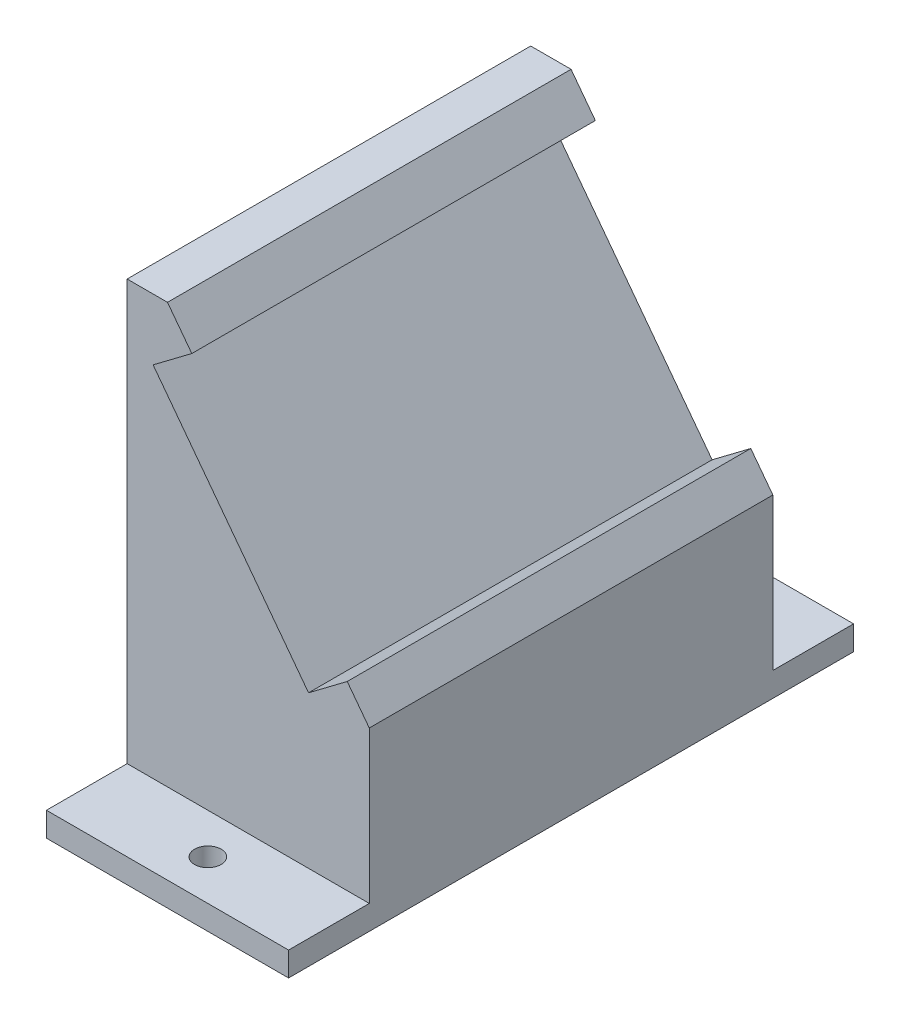
SolidWorks part; units mm, degrees
ref_plane "前视基准面" through (0, 0, 0) normal (0, 0, 1) x (1, 0, 0)
ref_plane "上视基准面" through (0, 0, 0) normal (0, 1, 0) x (1, 0, 0)
ref_plane "右视基准面" through (0, 0, 0) normal (1, 0, 0) x (0, 0, -1)
sketch "草图1" plane through (0, 0, 0) normal (0, 0, 1) x (1, 0, 0)
  line L3 (-10, 55) -> (-15, 55)
  line L4 (-15, 0) -> (-15, 55)
  line L8 (15, 0) -> (15, 21.8239)
  line L9 (-11.7827, 47.3959) -> (7.4753, 21.8396)
  line L10 (-6.9909, 51.0068) -> (-11.7827, 47.3959)
  line L11 (7.4753, 21.8396) -> (12.2672, 25.4505)
  line L12 (-10, 55) -> (-6.9909, 51.0068)
  line L13 (12.2672, 25.4505) -> (15, 21.8239)
  line L14 (-15, 0) -> (15, 0)
  point P13 (0, 0)
  dimension "D1" = 5
  dimension "D2" = 55
  dimension "D3" = 90
  dimension "D4" = 5
  dimension "D5" = 90
  dimension "D6" = 6
  dimension "D7" = 32
  dimension "D8" = 30
  dimension "D9" = 90
  dimension "D10" = 127
extrude "凸台-拉伸1" add sketch "草图1" along normal blind 25 and the other way blind 25 contours L4 L3 L12 L10 L9 L11 L13 L8 L14
sketch "草图2" plane through (0, 0, 25) normal (0, 0, 1) x (1, 0, 0)
  line L0 (15, 0) -> (15, 21.8239) construction
  line L1 (-15, 0) -> (15, 0)
  line L2 (-15, 0) -> (-15, 3)
  line L3 (-15, 3) -> (15, 3)
  line L4 (15, 0) -> (15, 3)
  dimension "D1" = 3
extrude "凸台-拉伸2" add sketch "草图2" along normal blind 10
sketch "草图3" plane through (0, 3, 0) normal (0, 1, 0) x (1, 0, 0)
  line L0 (15, -35) -> (-15, -35) construction
  circle A0 centre (0, -30) radius 1.65
  dimension "D1" = 3.3
  dimension "D2" = 5
extrude "切除-拉伸1" cut sketch "草图3" against normal up to surface (3 mm away) contours A0 up to face at (0, 0, 5)
mirror "镜向1" about plane through (0, 0, 0) normal (0, 0, 1) of "切除-拉伸1", "凸台-拉伸2"
